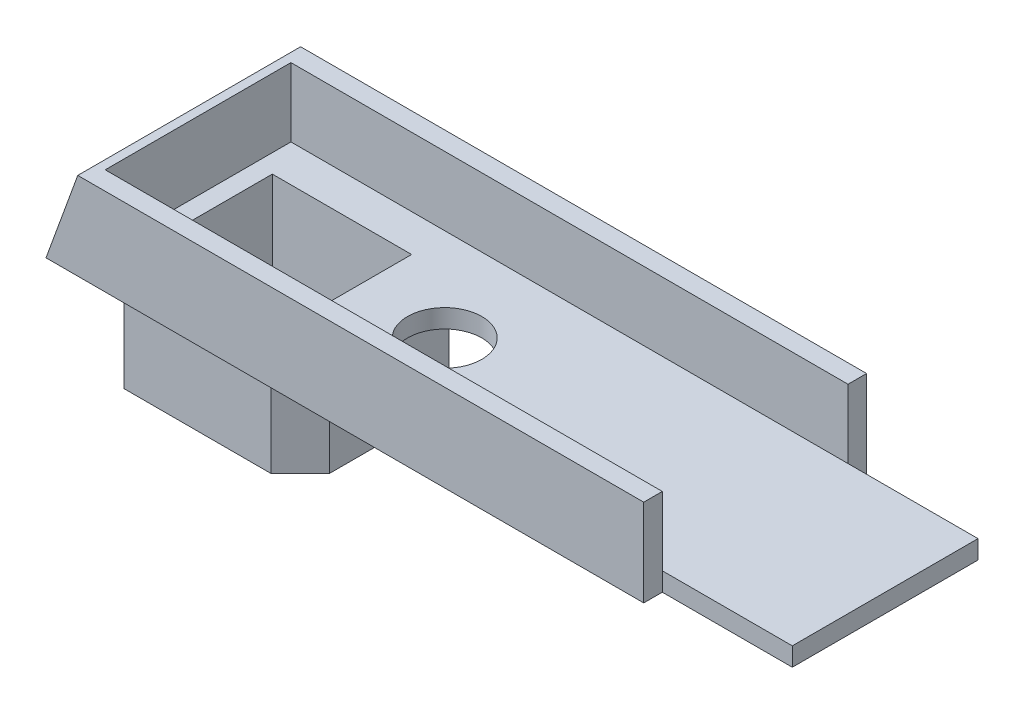
SolidWorks part; units mm, degrees
ref_plane "前视基准面" through (0, 0, 0) normal (0, 0, 1) x (1, 0, 0)
ref_plane "上视基准面" through (0, 0, 0) normal (0, 1, 0) x (1, 0, 0)
ref_plane "右视基准面" through (0, 0, 0) normal (1, 0, 0) x (0, 0, -1)
sketch "草图1" plane through (0, 0, 0) normal (0, 1, 0) x (1, 0, 0)
  line L0 (-12.5242, -6.4845) -> (-12.5242, -12.4845)
  line L1 (-13.5242, -4.4845) -> (-4.0242, -4.4845) construction
  line L2 (-13.5242, -4.4845) -> (-13.5242, -14.4845) construction
  line L3 (-13.5242, -14.4845) -> (-4.0242, -14.4845) construction
  line L4 (23.4758, -4.4845) -> (23.4758, -14.4845)
  line L5 (-12.5242, -12.4845) -> (-6.0242, -12.4845)
  line L6 (-5.0242, -11.4845) -> (-5.0242, -6.4845)
  line L7 (-5.0242, -6.4845) -> (-12.5242, -6.4845)
  line L8 (-6.0242, -12.4845) -> (-5.0242, -11.4845)
  line L9 (-53.0418, -9.4845) -> (30.158, -9.4845) construction
  line L13 (3.9758, -4.4845) -> (23.4758, -4.4845) construction
  line L17 (3.9758, -14.4845) -> (23.4758, -14.4845) construction
  line L18 (-4.0242, -3.4845) -> (-14.5242, -3.4845)
  line L19 (-14.5242, -3.4845) -> (-14.5242, -15.4845)
  line L20 (-14.5242, -15.4845) -> (-4.0242, -15.4845)
  line L21 (2.9758, -3.4845) -> (16.4758, -3.4845)
  line L22 (16.4758, -3.4845) -> (16.4758, -4.4845)
  line L23 (16.4758, -15.4845) -> (16.4758, -14.4845)
  line L24 (2.9758, -15.4845) -> (16.4758, -15.4845)
  line L25 (16.4758, -4.4845) -> (23.4758, -4.4845)
  line L26 (23.4758, -14.4845) -> (16.4758, -14.4845)
  line L27 (-4.0242, -15.4845) -> (2.9758, -15.4845)
  line L28 (-4.0242, -3.4845) -> (2.9758, -3.4845)
  point P12 (23.4758, -9.4845)
  dimension "D1" = 37
  dimension "D2" = 10
  dimension "D3" = 6
  dimension "D4" = 2
  dimension "D5" = 7.5
  dimension "D6" = 135
  dimension "D7" = 1
  dimension "D8" = 5
  dimension "D10" = 1
  dimension "D11" = 1
  dimension "D12" = 1
  dimension "D14" = 12.5
extrude "凸台-拉伸1" add sketch "草图1" along normal blind 1
sketch "草图2" plane through (0, 0, 0) normal (0, -1, 0) x (1, 0, 0)
  line L0 (-12.5242, 12.4845) -> (-6.0242, 12.4845)
  line L1 (-12.5242, 12.4845) -> (-6.0242, 12.4845) construction
  line L2 (-6.0242, 12.4845) -> (-5.0242, 11.4845) construction
  line L3 (-6.0242, 12.4845) -> (-5.0242, 11.4845)
  line L4 (-5.0242, 11.4845) -> (-5.0242, 6.4845)
  line L5 (-5.0242, 6.4845) -> (-12.5242, 6.4845)
  line L6 (-12.5242, 6.4845) -> (-12.5242, 12.4845)
  line L7 (-13.5242, 5.4845) -> (-13.5242, 13.4845)
  line L8 (-13.5242, 13.4845) -> (-5.61, 13.4845)
  line L9 (-5.61, 13.4845) -> (-4.0242, 11.8987)
  line L10 (-4.0242, 11.8987) -> (-4.0242, 5.4845)
  line L11 (-4.0242, 5.4845) -> (-13.5242, 5.4845)
  dimension "D1" = 1
extrude "凸台-拉伸2" add sketch "草图2" along normal blind 6
sketch "草图3" plane through (0, 1, 0) normal (0, 1, 0) x (1, 0, 0)
  line L1 (-18.2722, -9.4845) -> (28.1646, -9.4845) construction
  line L2 (-14.5242, -3.4845) -> (-14.5242, -15.4845) construction
  circle A0 centre (-0.2442, -9.4845) radius 2
  dimension "D1" = 4
  dimension "D2" = 14.28
extrude "切除-拉伸1" cut sketch "草图3" against normal blind 1
sketch "草图4" plane through (0, 1, 0) normal (0, 1, 0) x (1, 0, 0)
  line L0 (-14.5242, -3.4845) -> (16.4758, -3.4845)
  line L1 (16.4758, -3.4845) -> (16.4758, -4.4845)
  line L2 (16.4758, -4.4845) -> (-13.5242, -4.4845)
  line L3 (-14.5242, -3.4845) -> (-14.5242, -15.4845)
  line L4 (-14.5242, -15.4845) -> (16.4758, -15.4845)
  line L5 (16.4758, -15.4845) -> (16.4758, -14.4845)
  line L6 (16.4758, -14.4845) -> (-13.5242, -14.4845)
  line L7 (-13.5242, -14.4845) -> (-13.5242, -4.4845)
  dimension "D1" = 1
extrude "凸台-拉伸3" add sketch "草图4" along normal blind 3.7
sketch "草图5" plane through (0, 4.7, 0) normal (0, 1, 0) x (1, 0, 0)
  line L0 (-14.5242, -3.4845) -> (-14.5242, -15.4845)
  line L1 (-14.5242, -15.4845) -> (-4.0242, -15.4845)
  line L2 (-14.5242, -15.4845) -> (16.4758, -15.4845) construction
  line L3 (-14.5242, -3.4845) -> (-4.0242, -3.4845)
  line L4 (16.4758, -3.4845) -> (-14.5242, -3.4845) construction
  line L5 (-4.0242, -3.4845) -> (-4.0242, -10.3045)
  line L6 (-6.7242, -10.3045) -> (-6.7242, -12.8045)
  line L7 (-6.7242, -12.8045) -> (-4.0242, -12.8045)
  line L9 (-4.0242, -10.3045) -> (-6.7242, -10.3045)
  line L10 (-4.0242, -12.8045) -> (-4.0242, -15.4845)
  dimension "D1" = 7.8
  dimension "D2" = 2.68
  dimension "D3" = 2.5
  dimension "D4" = 2.7
sketch "草图6" plane through (0, 1, 0) normal (0, 1, 0) x (1, 0, 0)
  line L0 (-14.5242, -3.4845) -> (-14.5242, -15.4845) construction
  line L2 (-17.6881, -9.4845) -> (25.119, -9.4845) construction
  point P0 (-14.5242, -9.4845)
sketch "草图7" plane through (0, 0, 15.4845) normal (0, 0, 1) x (1, 0, 0)
  line L0 (-14.5242, 0) -> (-14.5242, 4.7)
  line L1 (-14.5242, 4.7) -> (-16.2348, 0)
  line L3 (-16.2348, 0) -> (-14.5242, 0)
  dimension "D1" = 20
extrude "凸台-拉伸4" add sketch "草图7" against normal blind 12
sketch "草图8" plane through (0, 0, 15.4845) normal (0, 0, 1) x (1, 0, 0)
  line L0 (-14.5242, 4.7) -> (-16.2348, 0)
  line L1 (-16.2348, 0) -> (-15.7134, 0)
  line L2 (-16.2348, 0) -> (16.4758, 0) construction
  line L3 (-15.7134, 0) -> (-14.0027, 4.7)
  line L4 (-14.5242, 4.7) -> (-4.0242, 4.7) construction
  line L5 (-14.0027, 4.7) -> (-14.5242, 4.7)
  dimension "D1" = 0.49
extrude "切除-拉伸2" cut sketch "草图8" against normal blind 12
